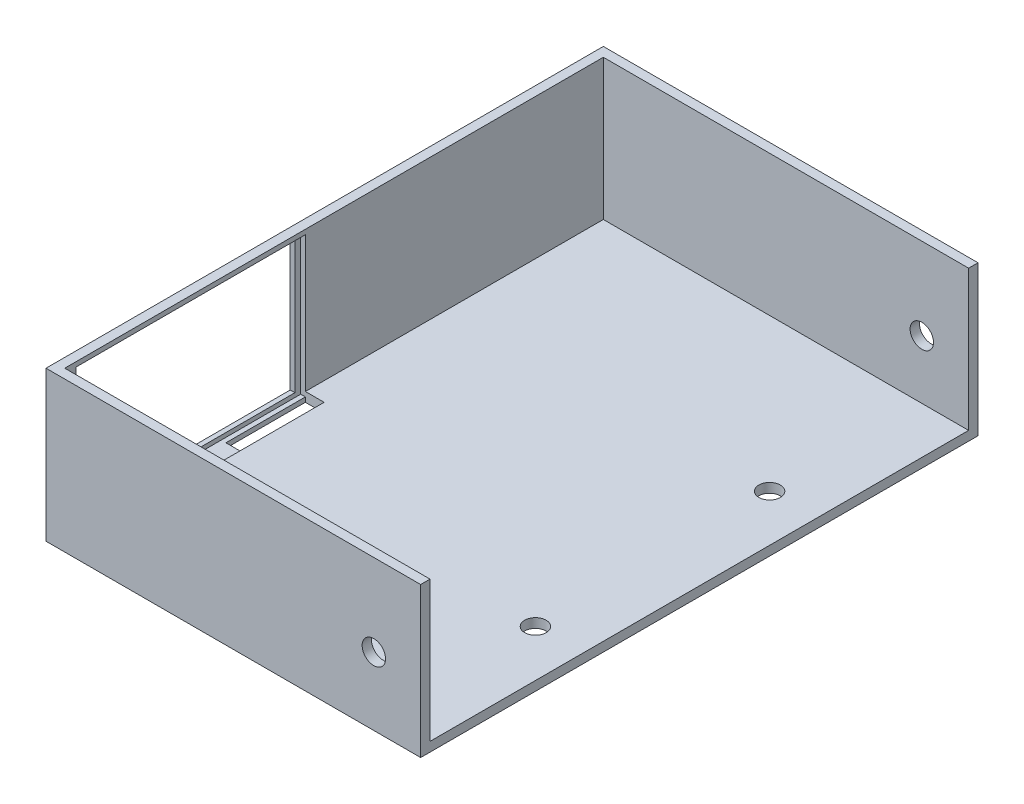
SolidWorks part; units mm, degrees
ref_plane "Front Plane" through (0, 0, 0) normal (0, 0, 1) x (1, 0, 0)
ref_plane "Top Plane" through (0, 0, 0) normal (0, 1, 0) x (1, 0, 0)
ref_plane "Right Plane" through (0, 0, 0) normal (1, 0, 0) x (0, 0, -1)
sketch "Sketch1" plane through (0, 0, 0) normal (0, 1, 0) x (1, 0, 0)
  line L1 (-40, -59.5) -> (40, -59.5)
  line L2 (-40, -59.5) -> (-40, 59.5)
  line L3 (-40, 59.5) -> (40, 59.5)
  line L4 (40, -59.5) -> (40, 59.5)
  line L5 (-40, -59.5) -> (40, 59.5) construction
  line L6 (-40, 59.5) -> (40, -59.5) construction
  point P0 (0, 0)
  dimension "D1" = 119
  dimension "D2" = 80
extrude "Boss-Extrude1" add sketch "Sketch1" along normal blind 32
sketch "Sketch2" plane through (0, 32, 0) normal (0, 1, 0) x (1, 0, 0)
  line L0 (40, -59.5) -> (40, 59.5) construction
  line L1 (40, 57.5) -> (-38, 57.5)
  line L2 (40, 57.5) -> (40, -57.5)
  line L3 (40, -57.5) -> (-38, -57.5)
  line L4 (-38, 57.5) -> (-38, -57.5)
  line L5 (40, 59.5) -> (-40, 59.5) construction
  line L6 (-40, -59.5) -> (40, -59.5) construction
  line L7 (-40, 59.5) -> (-40, -59.5) construction
  dimension "D1" = 2
  dimension "D2" = 2
  dimension "D3" = 2
extrude "Cut-Extrude1" cut sketch "Sketch2" against normal offset from surface (30 mm away) 2 up to face at (0, 0, 0)
sketch "Sketch3" plane through (0, 0, 59.5) normal (0, 0, 1) x (1, 0, 0)
  line L0 (40, 32) -> (40, 0) construction
  line L2 (-40, 0) -> (40, 0) construction
  circle A0 centre (30, 14.5) radius 2.5
  dimension "D1" = 5
  dimension "D2" = 10
  dimension "D3" = 14.5
extrude "Cut-Extrude2" cut sketch "Sketch3" against normal through all both and the other way through all
sketch "Sketch4" plane through (-38, 0, 0) normal (1, 0, 0) x (0, 0, -1)
  line L1 (-55.0557, 30.1) -> (-7.3557, 30.1)
  line L2 (-55.0557, 30.1) -> (-55.0557, 1.9)
  line L3 (-55.0557, 1.9) -> (-7.3557, 1.9)
  line L4 (-7.3557, 30.1) -> (-7.3557, 1.9)
  line L5 (-59.5, 16) -> (59.5, 16) construction
  line L6 (-59.5, 32) -> (-59.5, 0) construction
  line L7 (59.5, 32) -> (59.5, 0) construction
  point P10 (-7.3557, 16)
  dimension "D1" = 28.2
  dimension "D2" = 47.7
extrude "Cut-Extrude4" cut sketch "Sketch4" against normal blind 10
sketch "Sketch5" plane through (0, 2, 0) normal (0, 1, 0) x (1, 0, 0)
  line L1 (-39, -6.116) -> (-34, -6.116)
  line L2 (-39, -6.116) -> (-39, -55.0557)
  line L3 (-39, -55.0557) -> (-34, -55.0557)
  line L4 (-34, -6.116) -> (-34, -55.0557)
  line L6 (-40, -55.0557) -> (-38, -55.0557) construction
  line L7 (-40, -55.0557) -> (-40, -7.3557) construction
  point P6 (0, 0)
  dimension "D1" = 1
  dimension "D2" = 5
extrude "Cut-Extrude5" cut sketch "Sketch5" against normal blind 1 and the other way offset from surface 1 other way up to face at (0.5, 32, 0)
sketch "Sketch6" plane through (0, 1, 0) normal (0, 1, 0) x (1, 0, 0)
  line L0 (-34, -55.0557) -> (-34, -6.116) construction
  line L1 (-34, -6.116) -> (-38, -6.116)
  line L2 (-34, -6.116) -> (-34, -23.0858)
  line L3 (-34, -23.0858) -> (-38, -23.0858)
  line L4 (-38, -6.116) -> (-38, -23.0858)
  line L5 (-38, -55.0557) -> (-34, -55.0557)
  line L6 (-38, -55.0557) -> (-38, -38.0858)
  line L7 (-38, -38.0858) -> (-34, -38.0858)
  line L8 (-34, -55.0557) -> (-34, -38.0858)
  line L9 (-38, 57.5) -> (-38, -57.5) construction
  line L10 (-34, -6.116) -> (-39, -6.116) construction
  point P12 (-38, -6.116)
  point P18 (-34, -30.5858)
  dimension "D1" = 15
  dimension "D2" = 7.5
extrude "Cut-Extrude6" cut sketch "Sketch6" against normal blind 2
sketch "Sketch7" plane through (0, 0, 0) normal (0, -1, 0) x (1, 0, 0)
  line L0 (40, 59.5) -> (40, -59.5) construction
  line L1 (-40, 59.5) -> (40, 59.5) construction
  circle A0 centre (30, 25) radius 2.3
  circle A1 centre (30, -25) radius 2.3
  dimension "D1" = 10
  dimension "D3" = 4.6
  dimension "D4" = 50
  dimension "D2" = 34.5
extrude "Cut-Extrude7" cut sketch "Sketch7" against normal through all
